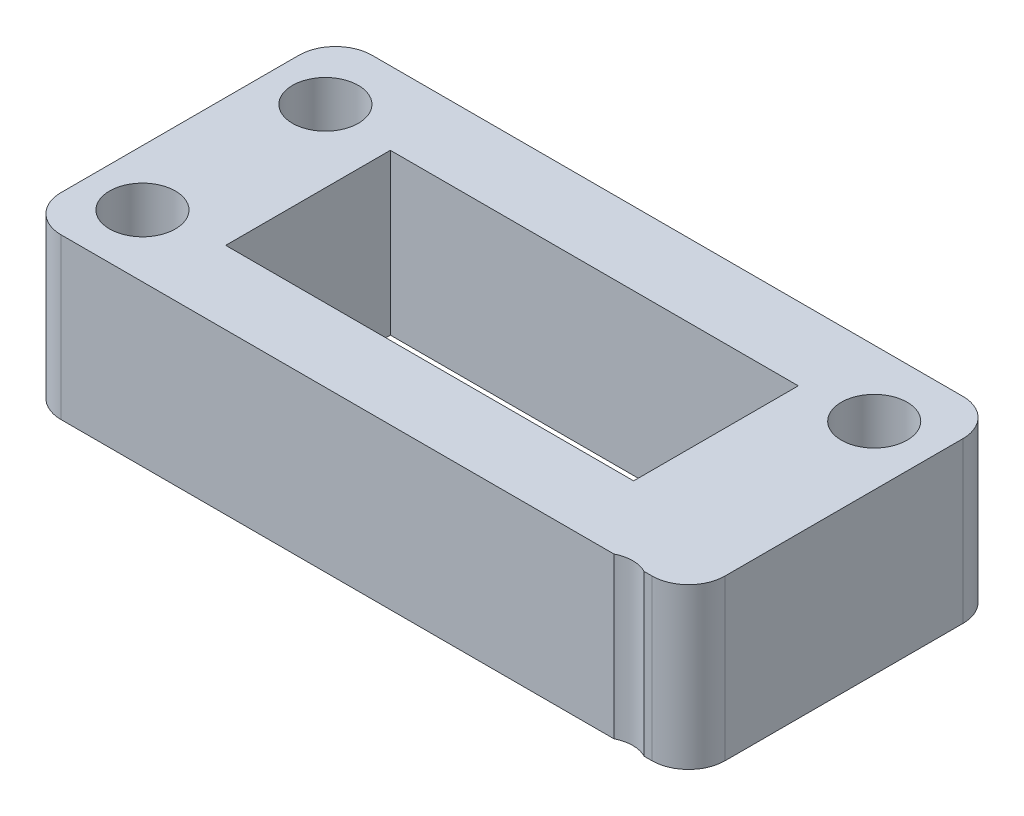
SolidWorks part; units mm, degrees
ref_plane "Front Plane" through (0, 0, 0) normal (0, 0, 1) x (1, 0, 0)
ref_plane "Top Plane" through (0, 0, 0) normal (0, 1, 0) x (1, 0, 0)
ref_plane "Right Plane" through (0, 0, 0) normal (1, 0, 0) x (0, 0, -1)
sketch "Sketch1" plane through (0, 0, 0) normal (0, 1, 0) x (1, 0, 0)
  line L0 (0, 0) -> (36.3, 0)
  line L1 (36.3, 0) -> (36.3, 17)
  line L2 (36.3, 17) -> (0, 17)
  line L3 (0, 17) -> (0, 0)
  line L4 (7, 13) -> (7, 4)
  line L5 (7, 4) -> (29.3, 4)
  line L6 (29.3, 4) -> (29.3, 13)
  line L7 (29.3, 13) -> (7, 13)
  line L8 (0, 8.5) -> (36.3, 8.5) construction
  line L9 (18.15, 0) -> (18.15, 17) construction
  point P13 (18.15, 13)
  point P14 (29.3, 8.5)
  dimension "D1" = 7
  dimension "D2" = 4
  dimension "D3" = 36.3
  dimension "D4" = 17
extrude "Boss-Extrude1" add sketch "Sketch1" along normal blind 8.75
sketch "Sketch2" plane through (0, 8.75, 0) normal (0, 1, 0) x (1, 0, 0)
  point P0 (3.05, 3.4)
  point P6 (33.05, -1.6)
  point P9 (33.05, 13.4)
  point P15 (3.05, 13.4)
hole_wizard "M3 Clearance Hole1" positions "Sketch2" profile "Sketch3" hole size "M3" standard "ANSI Metric" end condition through all
sketch "Sketch3" plane through (3.05, 8.75, -3.4) normal (1, 0, 0) x (0, 0, 1)
  line L0 (0, 0) -> (0, 8.75)
  line L1 (0, 8.75) -> (1.8, 8.75)
  line L2 (1.8, 8.75) -> (1.8, 0)
  line L5 (1.8, 0) -> (0, 0)
  line L11 (0, -6.35) -> (0, 107.95) construction
  dimension "Thru Hole Dia." = 3.6
  dimension "Thru Hole Depth" = 8.75
fillet "Fillet1" radius 2 4 edges at (0, 4.375, -17) (36.3, 4.375, -17) (36.3, 4.375, 0) (0, 4.375, 0)
